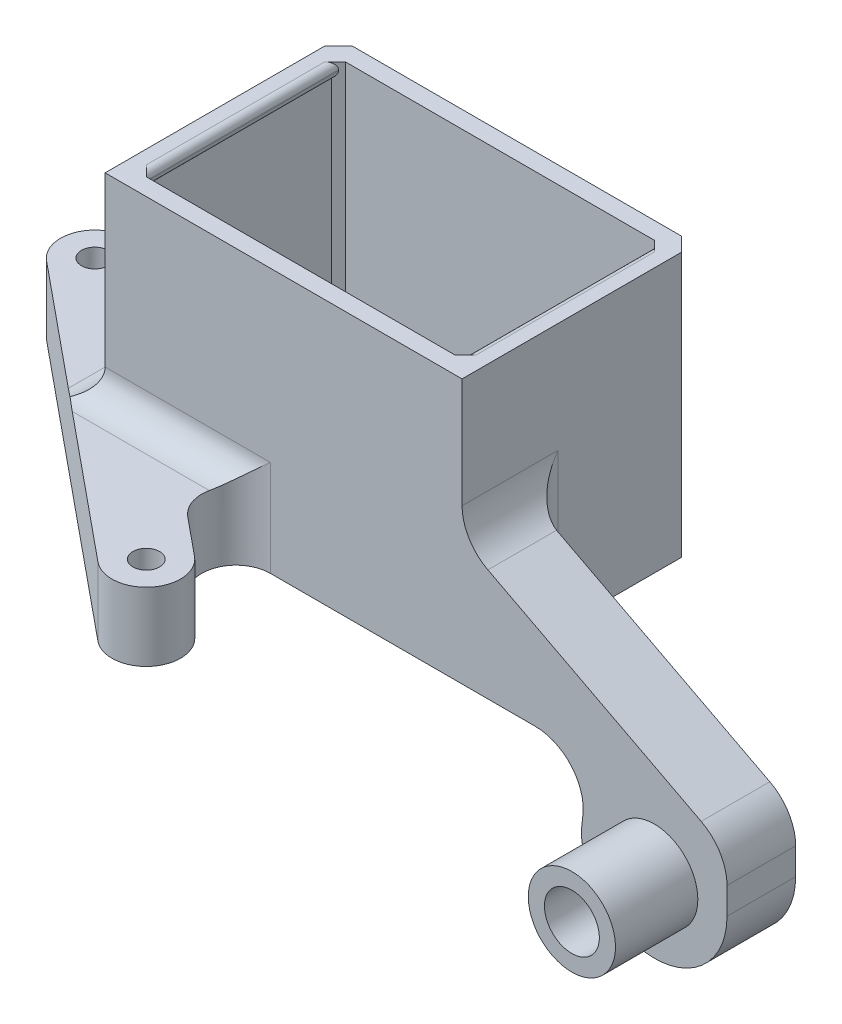
SolidWorks part; units mm, degrees
ref_plane "Plan de face" through (0, 0, 0) normal (0, 0, 1) x (1, 0, 0)
ref_plane "Plan de dessus" through (0, 0, 0) normal (0, 1, 0) x (1, 0, 0)
ref_plane "Plan de droite" through (0, 0, 0) normal (1, 0, 0) x (0, 0, -1)
sketch "Esquisse1" plane through (0, 0, 0) normal (0, 1, 0) x (1, 0, 0)
  line L0 (-23.5, 0) -> (23.5, 0) construction
  line L1 (23.5, -14.5) -> (-23.5, -14.5)
  line L2 (23.5, -14.5) -> (23.5, 14.5)
  line L3 (23.5, 14.5) -> (-23.5, 14.5)
  line L4 (-23.5, -14.5) -> (-23.5, 14.5)
  line L5 (23.5, -14.5) -> (-23.5, 14.5) construction
  line L6 (23.5, 14.5) -> (-23.5, -14.5) construction
  line L8 (26, -17) -> (-26, -17)
  line L9 (26, -17) -> (26, 17)
  line L10 (26, 17) -> (-26, 17)
  line L11 (-26, -17) -> (-26, 17)
  line L12 (26, -17) -> (-26, 17) construction
  line L13 (26, 17) -> (-26, -17) construction
  circle A0 centre (12.5, 0) radius 10.75
  point P0 (0, 0)
  point P8 (0, 0)
  point P15 (11.2946, 0)
  dimension "D6" = 21.5
  dimension "D1" = 29
  dimension "D2" = 47
  dimension "D3" = 2.5
  dimension "D4" = 2.5
  dimension "D5" = 11
extrude "Boss.-Extru.1" add sketch "Esquisse1" along normal blind 2 contours L4 L1 L2 L3 A0 | L11 L8 L9 L10 L1 L4 L3 L2 region at (-4.5384, 0, 0) region at (0, 0, 16.3787)
sketch "Esquisse2" plane through (0, 2, 0) normal (0, 1, 0) x (1, 0, 0)
  line L0 (-26, 17) -> (26, -17) construction
  line L2 (23.5, -14.5) -> (-23.5, -14.5)
  line L3 (23.5, -14.5) -> (23.5, 14.5)
  line L4 (23.5, 14.5) -> (-23.5, 14.5)
  line L5 (-23.5, -14.5) -> (-23.5, 14.5)
  line L6 (23.5, -14.5) -> (-23.5, 14.5) construction
  line L7 (23.5, 14.5) -> (-23.5, -14.5) construction
  line L15 (-26, 17) -> (-26, -17)
  line L16 (-26, -17) -> (26, -17)
  line L17 (26, -17) -> (26, 17)
  line L18 (26, 17) -> (-26, 17)
  line L19 (-26, 17) -> (-26, -17)
  line L20 (-26, -17) -> (26, -17)
  line L21 (26, -17) -> (26, 17)
  line L22 (26, 17) -> (-26, 17)
  point P4 (0, 0)
  dimension "D2" = 2.5
  dimension "D3" = 2.5
  dimension "D1" = 0
extrude "Boss.-Extru.2" add sketch "Esquisse2" along normal blind 34.5
sketch "Esquisse4" plane through (0, 0, 0) normal (0, -1, 0) x (1, 0, 0)
  line L0 (12.5, 0) -> (-2.7526, 34.258)
  line L1 (-2.7526, 34.258) -> (-44.4946, 0)
  line L2 (-44.4946, 0) -> (12.5, 0)
  line L3 (-2.7526, 34.258) -> (-44.4946, 0) construction
  line L4 (0.4194, 30.393) -> (-41.3226, -3.865)
  line L5 (-5.9247, 38.123) -> (-47.6666, 3.865)
  arc A0 (0.4194, 30.393) -> (-5.9247, 38.123) centre (-2.7526, 34.258) ccw
  arc A1 (-47.6666, 3.865) -> (-41.3226, -3.865) centre (-44.4946, 0) ccw
  circle A2 centre (-44.4946, 0) radius 1.95
  circle A3 centre (-2.7526, 34.258) radius 1.95
  point P4 (-23.6236, 17.129)
  line M5 (-26, 17) -> (-26, -17)
  line M8 (26, 17) -> (-26, 17)
  dimension "D4" = 3.9
  dimension "D5" = 3.9
  dimension "D1" = 37.5
  dimension "D2" = 54
  dimension "D3" = 66
  dimension "D6" = 10
extrude "Boss.-Extru.3" add sketch "Esquisse4" against normal blind 10 contours A3 L0 L4 A0 L5 A1 L2 A2 L1 M5 M8 | A3 L1 L4 L0 M8 | A2 L2 L4 L1 M5 region at (-11.0712, 0, 24.3227) region at (-25.3148, 0, 18.0257) region at (-33.3163, 0, 6.1983)
fillet "Congé1" radius 5 2 edges at (-26, 5, 8.7103) (-15.8994, 5, 17)
chamfer "Chanfrein1" distance 1 angle 45 4 edges at (-23.5, 19.25, -14.5) (23.5, 19.25, -14.5) (23.5, 19.25, 14.5) (-23.5, 19.25, 14.5)
chamfer "Chanfrein2" distance 2 angle 45 2 edges at (26, 18.25, -17) (-26, 18.25, -17)
fillet "Congé4" radius 4 2 edges at (-13.9628, 10, 17) (-26, 10, 7.5693)
sketch "Esquisse3" plane through (0, 0, 17) normal (0, 0, 1) x (1, 0, 0)
  line L0 (26, 0) -> (-1.9257, 0) construction
  line L1 (54, -10) -> (54, 0)
  line L2 (54, 0) -> (26, 0)
  line L3 (64.6, -10) -> (64.6, -1.87)
  line L4 (64.6, -1.87) -> (26, 18.25)
  line L5 (26, 36.5) -> (26, 0) construction
  line L13 (-26, 36.5) -> (-26, 14)
  line L14 (-26, 14) -> (-1.9257, 14)
  line L15 (-1.9257, 14) -> (-1.9257, 0)
  line L16 (-1.9257, 0) -> (26, 0)
  line L17 (26, 0) -> (26, 36.5)
  line L18 (26, 36.5) -> (-26, 36.5)
  line L19 (-26, 36.5) -> (-26, 14)
  line L20 (-26, 14) -> (-1.9257, 14)
  line L21 (-1.9257, 14) -> (-1.9257, 0)
  line L22 (-1.9257, 0) -> (26, 0)
  line L23 (26, 0) -> (26, 36.5)
  line L24 (26, 36.5) -> (-26, 36.5)
  circle A0 centre (54, -10) radius 6.1
  circle A2 centre (54, -10) radius 10.6
  point P15 (65.9283, -10)
  point P17 (64.85, -10)
  line M2 (26, 0) -> (26, 36.5)
  dimension "D3" = 12.2
  dimension "D4" = 0
  dimension "D5" = 4.5
  dimension "D1" = 10
  dimension "D2" = 28
extrude "Boss.-Extru.4" add sketch "Esquisse3" against normal blind 10 contours L3 L4 L2 M2 | A0 region at (59.9542, -1.5952, 17) region at (38.7149, 5.7171, 17)
fillet "Congé5" radius 7 3 edges at (26, 18.25, 12) (64.6, -1.87, 12) (50.4843, 0, 12)
fillet "Congé6" radius 4 1 edges at (26, 11.2476, 7)
sketch "Esquisse5" plane through (0, 0, 7) normal (0, 0, -1) x (-1, 0, 0)
  circle A0 centre (-54, -10) radius 6.35
extrude "Boss.-Extru.5" add sketch "Esquisse5" against normal blind 22
sketch "Esquisse6" plane through (0, 0, 7) normal (0, 0, -1) x (-1, 0, 0)
  circle A6 centre (-54, -10) radius 10.85
  circle A7 centre (-54, -10) radius 8
  circle A8 centre (-54, -2) radius 0.875
  circle A10 centre (-46, -10) radius 0.875
  circle A11 centre (-54, -18) radius 0.875
  circle A12 centre (-62, -10) radius 0.875
  point P14 (-72.3209, -17.7511)
  point P16 (-54, -10)
  dimension "D1" = 16
  dimension "D2" = 1.75
  dimension "D3" = 4
extrude "Enlèv. mat.-Extru.1" cut sketch "Esquisse6" against normal blind 8 and the other way blind 10 contours A7 A11 | A7 A10 | A7 A10 | A7 A12 | A7 A12 | A7 A8 | A7 A8 | A7 A11 region at (46.3798, -10, 7) region at (45.6374, -10, 7) region at (54, -2.3798, 7) region at (54, -1.6374, 7) region at (54, -18.3626, 7) region at (54, -17.6202, 7) region at (61.6202, -10, 7) region at (62.3626, -10, 7)
sketch "Esquisse7" plane through (0, 0, 7) normal (0, 0, -1) x (-1, 0, 0)
  circle A0 centre (-54, -10) radius 4
  arc A1 (-64.6, -10) -> (-43.5551, -8.1932) centre (-54, -10) ccw construction
  point P3 (0, 0)
  dimension "D1" = 8
extrude "Enlèv. mat.-Extru.2" cut sketch "Esquisse7" against normal blind 26
sketch "Esquisse8" plane through (0, 36.5, 0) normal (0, 1, 0) x (1, 0, 0)
  line L0 (-23, 14) -> (-23, -14)
  line L1 (23, -14) -> (23, 14)
  line L6 (26, -17) -> (26, 15)
  line L7 (26, 15) -> (24, 17)
  line L8 (24, 17) -> (-24, 17)
  line L9 (-24, 17) -> (-26, 15)
  line L10 (-26, 15) -> (-26, -17)
  line L11 (-26, -17) -> (26, -17)
  line L12 (26, -17) -> (26, 15)
  line L13 (26, 15) -> (24, 17)
  line L14 (24, 17) -> (-24, 17)
  line L15 (-24, 17) -> (-26, 15)
  line L16 (-26, 15) -> (-26, -17)
  line L17 (-26, -17) -> (26, -17)
  line L20 (-22.5, -14.5) -> (22.5, -14.5)
  line L21 (-23.5, -13.5) -> (-22.5, -14.5)
  line L22 (-23.5, 13.5) -> (-23.5, -13.5)
  line L23 (-22.5, 14.5) -> (-23.5, 13.5)
  line L24 (22.5, 14.5) -> (-22.5, 14.5)
  line L25 (23.5, 13.5) -> (22.5, 14.5)
  line L26 (23.5, -13.5) -> (23.5, 13.5)
  line L27 (22.5, -14.5) -> (23.5, -13.5)
  line L28 (-22.5, -14.5) -> (22.5, -14.5)
  line L29 (-23.5, -13.5) -> (-22.5, -14.5)
  line L30 (-23.5, 13.5) -> (-23.5, -13.5)
  line L31 (-22.5, 14.5) -> (-23.5, 13.5)
  line L32 (22.5, 14.5) -> (-22.5, 14.5)
  line L33 (23.5, 13.5) -> (22.5, 14.5)
  line L34 (23.5, -13.5) -> (23.5, 13.5)
  line L35 (22.5, -14.5) -> (23.5, -13.5)
  line M15 (26, -17) -> (26, 15)
  line M16 (26, 15) -> (24, 17)
  line M17 (24, 17) -> (-24, 17)
  line M18 (-24, 17) -> (-26, 15)
  line M19 (-26, 15) -> (-26, -17)
  line M20 (-26, -17) -> (26, -17)
  line M21 (22.5, -14.5) -> (-22.5, -14.5)
  line M22 (-22.5, -14.5) -> (-23.5, -13.5)
  line M23 (-23.5, -13.5) -> (-23.5, 13.5)
  line M24 (-23.5, 13.5) -> (-22.5, 14.5)
  line M25 (-22.5, 14.5) -> (22.5, 14.5)
  line M26 (22.5, 14.5) -> (23.5, 13.5)
  line M27 (23.5, 13.5) -> (23.5, -13.5)
  line M28 (23.5, -13.5) -> (22.5, -14.5)
  dimension "D1" = 0
  dimension "D2" = 0
extrude "Boss.-Extru.6" add sketch "Esquisse8" along normal blind 2 contours M20 M15 M16 M17 M18 M19 M28 M21 M22 M23 M24 M25 M26 M27 | L1 M28 M27 M26 | L0 M24 M23 M22 region at (-23.2485, 36.5, 0) region at (23.2485, 36.5, 0) region at (0, 36.5, 16.3787)
fillet "Congé7" radius 1 4 edges at (-23, 38.5, 0) (23, 38.5, 0) (23, 36.5, 0) (-23, 36.5, 0)
